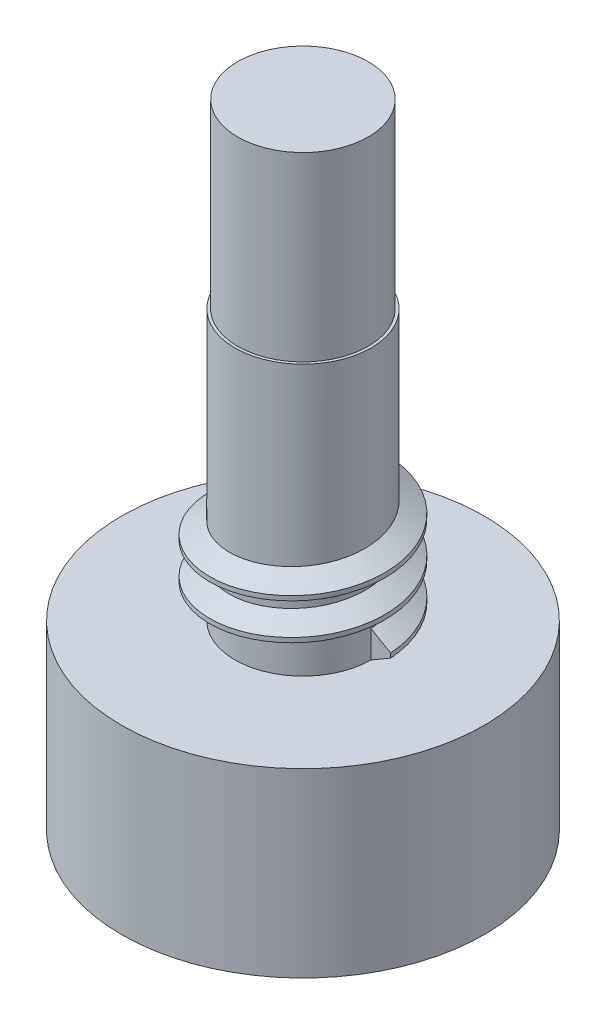
SolidWorks part; units mm, degrees
ref_plane "Front Plane" through (0, 0, 0) normal (0, 0, 1) x (1, 0, 0)
ref_plane "Top Plane" through (0, 0, 0) normal (0, 1, 0) x (1, 0, 0)
ref_plane "Right Plane" through (0, 0, 0) normal (1, 0, 0) x (0, 0, -1)
sketch "Sketch2" plane through (0, 0, 0) normal (0, 1, 0) x (1, 0, 0)
  circle A0 centre (0, 0) radius 6.35
  dimension "D1" = 12.7
extrude "Boss-Extrude1" add sketch "Sketch2" along normal blind 6.35
sketch "Sketch3" plane through (0, 6.35, 0) normal (0, 1, 0) x (1, 0, 0)
  circle A0 centre (0, 0) radius 2.3825
  dimension "D1" = 4.765
extrude "Boss-Extrude2" add sketch "Sketch3" along normal blind 15.8115
thread "Thread2" pitch 1.27 method extrude profile "Thread Profile2" start angle 0, offset 0, length 3.175, pitch 1.27, diameter 4.765
ref_plane "Plane2" through (2.3825, 6.35, 0) normal (0, 0, 1) x (1, 0, 0)
sketch "Thread Profile2" plane through (2.3825, 6.35, 0) normal (0, 0, 1) x (1, 0, 0)
  line L0 (0, 0) -> (0, 1.27) construction
  line L1 (0, 0) -> (0.6874, 0.3969)
  line L2 (0.6874, 0.3969) -> (0.6874, 0.5556)
  line L3 (0.6874, 0.5556) -> (0, 0.9525)
  line L4 (0.6874, 0.4762) -> (0, 0.4762) construction
  line L11 (0, 0) -> (0, 0.9525)
  point P2 (0, 0)
  dimension "Pitch" = 1.27
  dimension "Profile_Angle" = 60
  dimension "Profile_Land" = 0.1588
  dimension "Profile_Height" = 0.6874
sketch "Sketch4" plane through (0, 22.1615, 0) normal (0, 1, 0) x (1, 0, 0)
  circle A0 centre (0, 0) radius 2.286
  dimension "D1" = 4.572
extrude "Cut-Extrude1" cut sketch "Sketch4" against normal blind 6.35 flip side to cut
